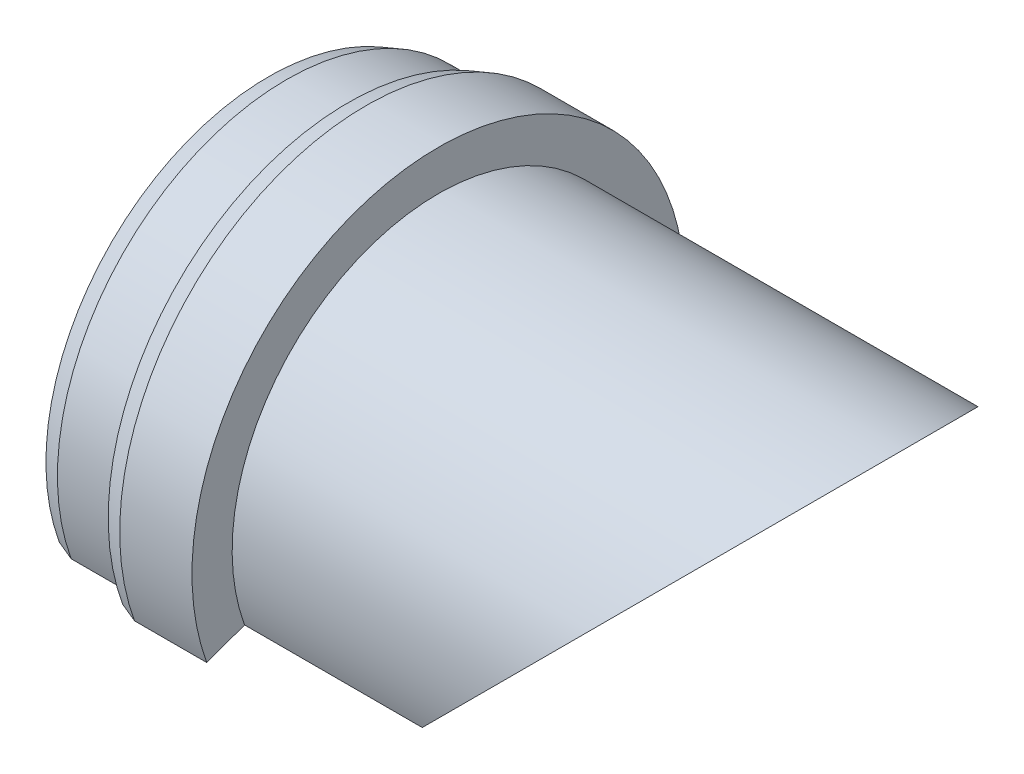
SolidWorks part; units mm, degrees
ref_plane "Front Plane" through (0, 0, 0) normal (0, 0, 1) x (1, 0, 0)
ref_plane "Top Plane" through (0, 0, 0) normal (0, 1, 0) x (1, 0, 0)
ref_plane "Right Plane" through (0, 0, 0) normal (1, 0, 0) x (0, 0, -1)
sketch "Sketch1" plane through (0, 0, 0) normal (0, 0, 1) x (1, 0, 0)
  line L0 (0, 0) -> (90.3238, 0) construction
  line L1 (172.74, 57.05) -> (47, 57.05)
  line L2 (47, 57.05) -> (47, 68.165)
  line L3 (47, 68.165) -> (22, 68.165)
  line L4 (22, 68.165) -> (22, 63.4)
  line L5 (22, 63.4) -> (0, 63.4)
  line L6 (0, 63.4) -> (0, 55.05)
  line L7 (0, 55.05) -> (172.74, 55.05)
  line L8 (172.74, 55.05) -> (172.74, 57.05)
  line L9 (182.74, 67.05) -> (-17.26, -132.95)
  line L10 (-17.26, -132.95) -> (182.74, -132.95)
  line L11 (182.74, -132.95) -> (182.74, 67.05)
  point P14 (69.5063, -74.4483)
  dimension "D1" = 136.33
  dimension "D2" = 126.8
  dimension "D3" = 114.1
  dimension "D4" = 2
  dimension "D5" = 22
  dimension "D6" = 25
  dimension "D7" = 125.74
  dimension "D8" = 45
  dimension "D9" = 10
  dimension "D10" = 200
revolve "Revolve1" add sketch "Sketch1" angle 360 about L0 region at (171.6175, 56.1725, 0) region at (172.0733, 55.7167, 0)
extrude "Cut-Extrude1" cut sketch "Sketch1<3>" against normal through all both and the other way through all contours L10 L11 L9 L8 L7 | L8 L9 L7 region at (116.0677, -66.2955, 0) region at (172.0733, 55.7167, 0)
sketch "Sketch1<3>" plane through (0, 0, 0) normal (0, 0, 1) x (1, 0, 0) same geometry as "Sketch1"
chamfer "Chamfer1" distance 5 angle 20 2 edges at (0, 0, 63.4) (22, 0, 68.165) first distance on face at (0, 0, 63.4) first distance on face at (22, 0, 68.165)
sketch "Sketch2" plane through (0, 0, 0) normal (1, 0, 0) x (0, 0, -1)
  line L0 (0, 0) -> (-302.2225, -110)
  line L1 (-302.2225, -110) -> (19.396, -110)
  line L2 (19.396, -110) -> (0, 0)
  line L3 (0, 0) -> (90.896, 0) construction
  line L4 (0, -150) -> (0, 0) construction
  point P6 (-178.763, -150)
  point P7 (-202.5311, -150)
  dimension "D1" = 80
  dimension "D2" = 150
  dimension "D3" = 20
  dimension "D4" = 110
extrude "Cut-Extrude3" cut sketch "Sketch2" against normal through all and the other way through all
